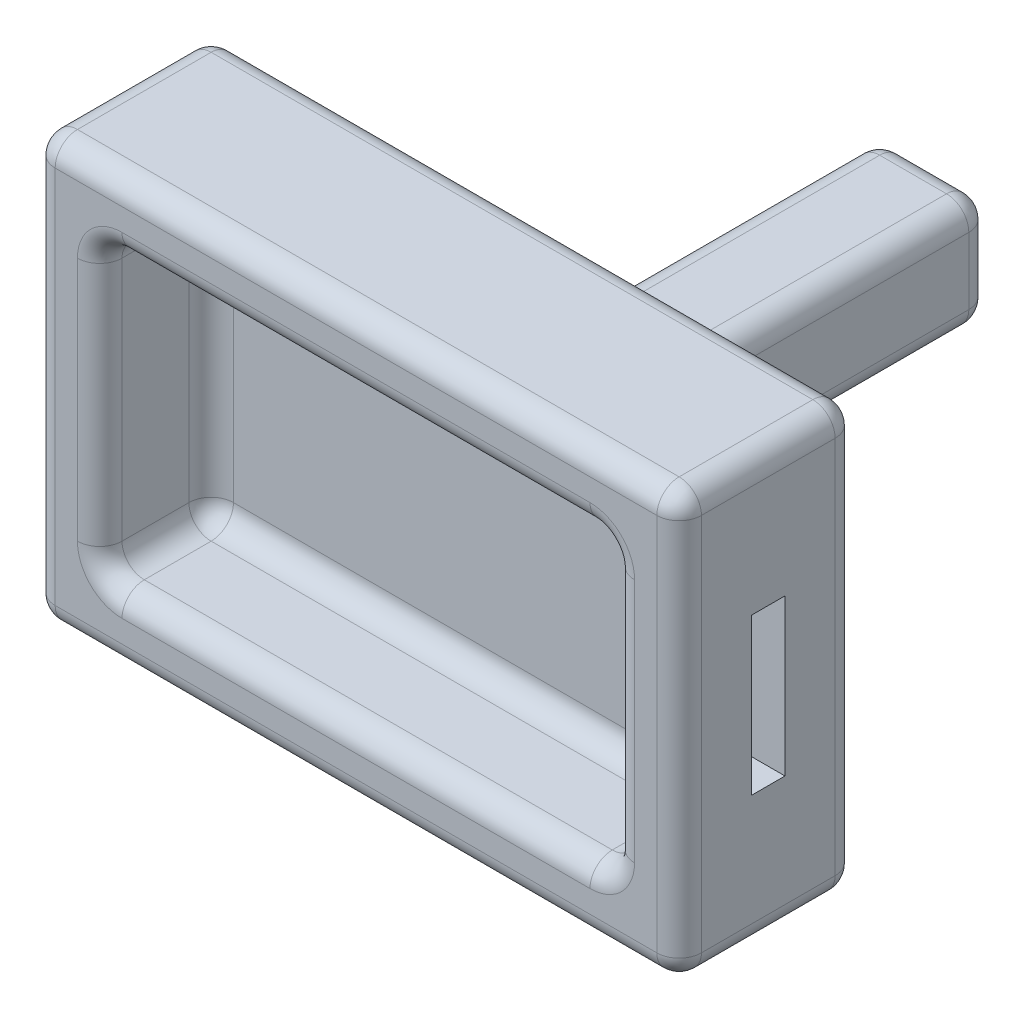
SolidWorks part; units mm, degrees
ref_plane "Front Plane" through (0, 0, 0) normal (0, 0, 1) x (1, 0, 0)
ref_plane "Top Plane" through (0, 0, 0) normal (0, 1, 0) x (1, 0, 0)
ref_plane "Right Plane" through (0, 0, 0) normal (1, 0, 0) x (0, 0, -1)
sketch "Sketch1" plane through (0, 0, 0) normal (0, 0, 1) x (1, 0, 0)
  line L0 (14.5, -9.5) -> (-14.5, -9.5)
  line L1 (11.5, -6.5) -> (-11.5, -6.5) construction
  line L2 (11.5, -6.5) -> (11.5, 6.5) construction
  line L3 (11.5, 6.5) -> (-11.5, 6.5) construction
  line L4 (-11.5, -6.5) -> (-11.5, 6.5) construction
  line L5 (11.5, -6.5) -> (-11.5, 6.5) construction
  line L6 (11.5, 6.5) -> (-11.5, -6.5) construction
  line L7 (-14.5, -9.5) -> (-14.5, 9.5)
  line L8 (14.5, 9.5) -> (-14.5, 9.5)
  line L9 (14.5, -9.5) -> (14.5, 9.5)
  point P0 (0, 0)
  dimension "D1" = 13
  dimension "D2" = 23
  dimension "D3" = 3
extrude "Boss-Extrude1" add sketch "Sketch1" along normal blind 3
sketch "Sketch2" plane through (0, 0, 3) normal (0, 0, 1) x (1, 0, 0)
  line L1 (11.5, -6.5) -> (-11.5, -6.5)
  line L2 (11.5, -6.5) -> (11.5, 6.5)
  line L3 (11.5, 6.5) -> (-11.5, 6.5)
  line L4 (-11.5, -6.5) -> (-11.5, 6.5)
  line L5 (11.5, -6.5) -> (-11.5, 6.5) construction
  line L6 (11.5, 6.5) -> (-11.5, -6.5) construction
  line L7 (14.5, -9.5) -> (-14.5, -9.5)
  line L8 (14.5, -9.5) -> (14.5, 9.5)
  line L9 (14.5, 9.5) -> (-14.5, 9.5)
  line L10 (-14.5, -9.5) -> (-14.5, 9.5)
  line L11 (14.5, -9.5) -> (-14.5, 9.5) construction
  line L12 (14.5, 9.5) -> (-14.5, -9.5) construction
  point P0 (0, 0)
  point P7 (0, 0)
extrude "Boss-Extrude2" add sketch "Sketch2" along normal blind 5
sketch "Sketch3" plane through (0, 0, 0) normal (0, 0, -1) x (-1, 0, 0)
  line L1 (-2.5, 2.5) -> (2.5, 2.5)
  line L2 (-2.5, 2.5) -> (-2.5, -2.5)
  line L3 (-2.5, -2.5) -> (2.5, -2.5)
  line L4 (2.5, 2.5) -> (2.5, -2.5)
  line L5 (-2.5, 2.5) -> (2.5, -2.5) construction
  line L6 (-2.5, -2.5) -> (2.5, 2.5) construction
  point P0 (0, 0)
  dimension "D2" = 5
extrude "Boss-Extrude3" add sketch "Sketch3" along normal blind 18
fillet "Fillet1" radius 1 36 edges at (-14.5, -9.5, 4) (-14.5, 0, 8) (-14.5, 9.5, 4) (-11.5, 0, 3) (0, -6.5, 3) (11.5, 0, 3) (0, 6.5, 3) (-11.5, 0, 8) (0, -6.5, 8) (11.5, 0, 8) (0, 6.5, 8) (-11.5, 6.5, 5.5) (11.5, -6.5, 5.5) (-11.5, -6.5, 5.5) (0, -9.5, 8) (14.5, 0, 8) (14.5, 0, 0) (0, 9.5, 0) (14.5, -9.5, 4) (14.5, 9.5, 4) (0, 9.5, 8) (-14.5, 0, 0) (0, -9.5, 0) (11.5, 6.5, 5.5) (2.5, 0, -18) (2.5, 0, 0) (2.5, -2.5, -9) (0, -2.5, -18) (0, -2.5, 0) (0, 2.5, -18) (2.5, 2.5, -9) (0, 2.5, 0) (-2.5, -2.5, -9) (-2.5, 0, -18) (-2.5, 2.5, -9) (-2.5, 0, 0)
sketch "Sketch4" plane through (14.5, 0, 0) normal (1, 0, 0) x (0, 0, -1)
  line L0 (0, 0) -> (-4, 0) construction
  line L2 (-3.25, -3.5) -> (-4.75, -3.5)
  line L3 (-3.25, -3.5) -> (-3.25, 3.5)
  line L4 (-3.25, 3.5) -> (-4.75, 3.5)
  line L5 (-4.75, -3.5) -> (-4.75, 3.5)
  line L6 (-3.25, -3.5) -> (-4.75, 3.5) construction
  line L7 (-3.25, 3.5) -> (-4.75, -3.5) construction
  dimension "D1" = 4
  dimension "D2" = 1.5
  dimension "D3" = 7
extrude "Cut-Extrude1" cut sketch "Sketch4" against normal blind 8
